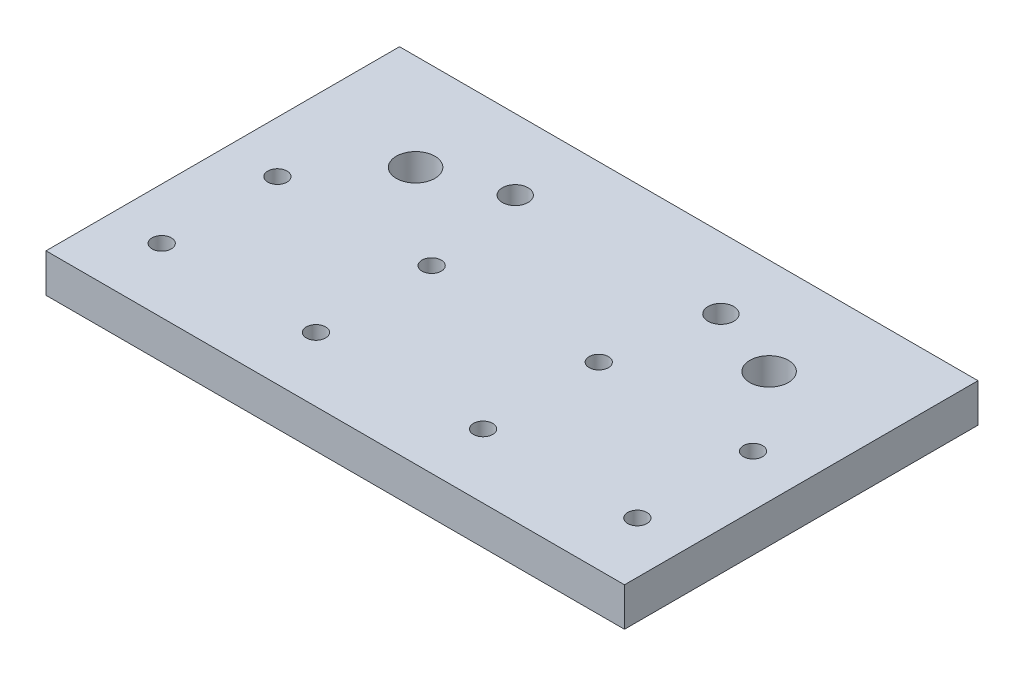
SolidWorks part; units mm, degrees
ref_plane "Front Plane" through (0, 0, 0) normal (0, 0, 1) x (1, 0, 0)
ref_plane "Top Plane" through (0, 0, 0) normal (0, 1, 0) x (1, 0, 0)
ref_plane "Right Plane" through (0, 0, 0) normal (1, 0, 0) x (0, 0, -1)
sketch "Sketch1" plane through (0, 0, 0) normal (0, 1, 0) x (1, 0, 0)
  line L0 (0, -383.892) -> (0, 18810.7071) construction
  line L1 (-45, 30) -> (45, 30)
  line L2 (-45, 30) -> (-45, -25)
  line L3 (-45, -25) -> (45, -25)
  line L4 (45, 30) -> (45, -25)
  line L7 (-383.892, 0) -> (18810.7071, 0) construction
  line L14 (25, -383.892) -> (25, 18810.7071) construction
  line L16 (13, -15) -> (37, -15) construction
  line L18 (13, -15) -> (13, 3) construction
  line L19 (13, 3) -> (37, 3) construction
  line L20 (37, -15) -> (37, 3) construction
  line L21 (13, -15) -> (37, 3) construction
  line L22 (13, 3) -> (37, -15) construction
  circle A0 centre (27.5, 15) radius 3
  circle A1 centre (-27.5, 15) radius 3
  circle A2 centre (37, 3) radius 1.5
  circle A3 centre (13, 3) radius 1.5
  circle A4 centre (37, -15) radius 1.5
  circle A5 centre (13, -15) radius 1.5
  circle A6 centre (-37, -15) radius 1.5
  circle A7 centre (-37, 3) radius 1.5
  circle A8 centre (-13, -15) radius 1.5
  circle A9 centre (-13, 3) radius 1.5
  point P0 (0, 0)
  point P19 (25, -6)
  dimension "D6" = 6
  dimension "D7" = 27.5
  dimension "D8" = 40
  dimension "D13" = 3
  dimension "D15" = 18
  dimension "D2" = 90
  dimension "D3" = 30
  dimension "D4" = 25
  dimension "D5" = 45
  dimension "D10" = 24
  dimension "D11" = 18
  dimension "D12" = 10
  dimension "D9" = 25
  dimension "D14" = 2
extrude "Boss-Extrude1" add sketch "Sketch1" along normal blind 6
sketch "Sketch2" plane through (0, 6, 0) normal (0, 1, 0) x (1, 0, 0)
  line L0 (45, -25) -> (45, 30) construction
  line L3 (0, -1000) -> (0, 49000) construction
  line L4 (45, 30) -> (-45, 30) construction
  circle A0 centre (16, 19) radius 2
  circle A3 centre (-16, 19) radius 2
  dimension "D1" = 11
  dimension "D2" = 4
  dimension "D3" = 29
extrude "Cut-Extrude1" cut sketch "Sketch2" against normal up to next
